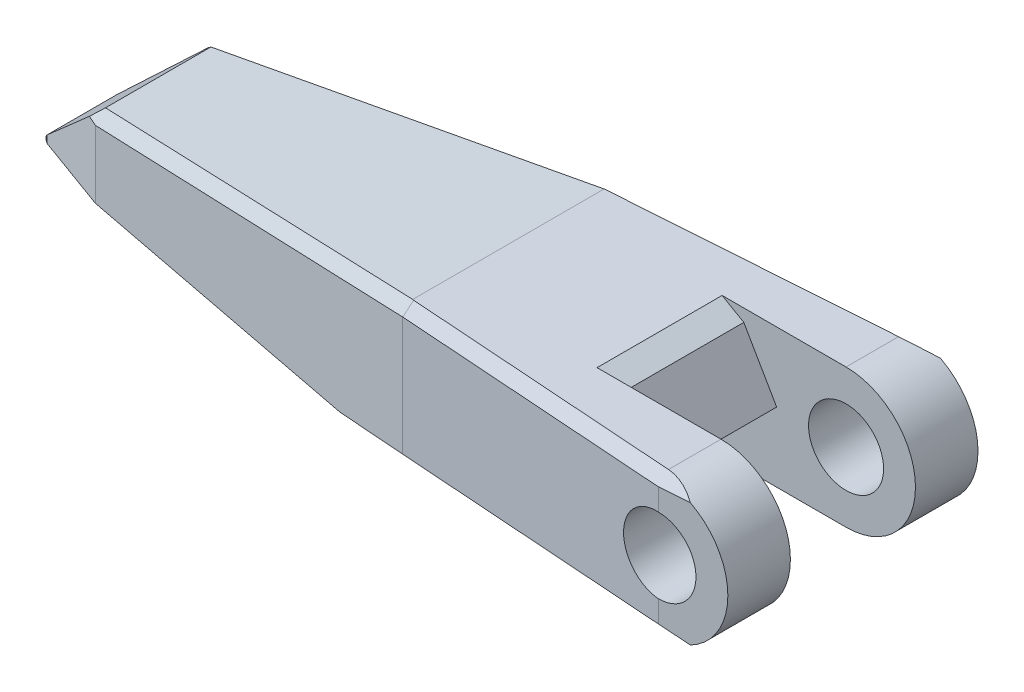
SolidWorks part; units mm, degrees
ref_plane "Alzado" through (0, 0, 0) normal (0, 0, 1) x (1, 0, 0)
ref_plane "Planta" through (0, 0, 0) normal (0, 1, 0) x (1, 0, 0)
ref_plane "Vista lateral" through (0, 0, 0) normal (1, 0, 0) x (0, 0, -1)
sketch "Croquis1" plane through (0, 0, 0) normal (0, 0, 1) x (1, 0, 0)
  line L0 (-56.8432, -15.5) -> (-41.8432, -15.5)
  line L1 (-41.8432, -15.5) -> (-41.8432, 0)
  line L3 (-41.8432, -15.5) -> (28.1568, -21.6242)
  line L4 (28.1568, -21.6242) -> (28.1568, 6.1242)
  line L5 (28.1568, 6.1242) -> (-41.8432, 0)
  line L6 (48.1568, 6.1242) -> (48.1568, -21.6242)
  line L7 (48.1568, -21.6242) -> (28.1568, -21.6242)
  line L8 (28.1568, 6.1242) -> (48.1568, 6.1242)
  line L9 (48.1568, 6.1242) -> (83.1568, 6.1242)
  line L10 (48.1568, -21.6242) -> (83.1568, -21.6242)
  line L11 (-57.0307, -14.0347) -> (-41.8432, 0)
  arc A0 (83.1568, -21.6242) -> (83.1568, 6.1242) centre (83.1568, -7.75) ccw
  circle A1 centre (83.1568, -7.75) radius 7.5
  ellipse E0 centre (-56.8686, -14.7363) end of major axis (-56.8941, -13.9726) minor radius 0.3641 (-57.0307, -14.0347) -> (-56.8432, -15.5) ccw
  point P12 (97.0311, -7.75)
  dimension "D8" = 15
  dimension "D1" = 15.5
  dimension "D2" = 15
  dimension "D3" = 90
  dimension "D4" = 85
  dimension "D5" = 85
  dimension "D6" = 70
  dimension "D7" = 20
  dimension "D9" = 27.7484
  dimension "D10" = 35
  dimension "D11" = 35
  dimension "D12" = 154.2636
extrude "Saliente-Extruir1" add sketch "Croquis1" along normal blind 50 contours L11 E0 L0 L1 | L4 L5 L1 L3 | L8 L4 L7 L6 | L10 A0 L9 L6 A1 region at (-47.3575, -10.2977, 0) region at (-3.539, -7.75, 0) region at (38.1568, -7.75, 0) region at (69.2849, -7.75, 0)
sketch "Croquis2" plane through (-0.3178, 3.633, 0) normal (-0.0872, 0.9962, 0) x (0.9962, 0.0872, 0)
  line L0 (83.3742, 0) -> (28.6289, -3.8282)
  line L1 (28.6289, -3.8282) -> (-41.6839, -12.4615)
  line L2 (28.6289, -3.8282) -> (28.5835, -46.1687)
  line L3 (28.5835, -50) -> (28.5835, 0) construction
  line L4 (-41.6839, -50) -> (-41.6839, 0) construction
  line L5 (-41.6839, -12.4615) -> (-41.6839, -37.5409)
  line L6 (28.5835, -46.1687) -> (83.3742, -50)
  line L7 (83.3742, -50) -> (83.3742, 0)
  line L8 (28.5835, 0) -> (83.3742, 0) construction
  line L9 (28.5835, -50) -> (83.3742, -50) construction
  line L10 (-41.6839, -37.5409) -> (28.5835, -46.1687)
  line L11 (28.5835, 0) -> (-41.6839, 0) construction
  line L12 (28.5835, -50) -> (-41.6839, -50) construction
  line L13 (-41.6839, -12.4615) -> (-58.0369, -18.4135)
  line L14 (-58.0369, -50) -> (-58.0369, 0) construction
  line L15 (-58.0369, -18.4135) -> (-58.0369, -31.5889)
  line L16 (-58.0369, -31.5889) -> (-41.6839, -37.5409)
  line L17 (-58.0369, -18.4135) -> (-58.3025, -18.4135)
  line L18 (-58.3025, 0) -> (-58.3025, -50) construction
  line L19 (-58.3025, -18.4135) -> (-58.3025, -31.5889)
  line L20 (-58.3025, -31.5889) -> (-58.0369, -31.5889)
  line L21 (-58.3025, -18.4135) -> (-58.3025, 0)
  line L22 (-58.3025, 0) -> (-41.6839, 0)
  line L23 (-41.6839, 0) -> (-41.6839, -12.4615)
  line L24 (-58.3025, -31.5889) -> (-58.3025, -50)
  line L25 (-58.3025, -50) -> (-41.6839, -50)
  line L26 (-41.6839, -50) -> (-41.6839, -37.5409)
  dimension "D1" = 4
  dimension "D2" = 4
  dimension "D3" = 42.3405
  dimension "D4" = 7
  dimension "D5" = 7
  dimension "D6" = 25.0794
  dimension "D7" = 70
  dimension "D8" = 70
sketch "Croquis6" plane through (0, 6.1242, 0) normal (0, 1, 0) x (1, 0, 0)
  line L0 (28.1568, 0) -> (28.1568, -3.846)
  line L1 (28.1568, -50) -> (28.1568, 0) construction
  line L2 (28.1568, -3.846) -> (83.1568, 0)
  line L3 (83.1568, 0) -> (28.1568, 0)
  line L4 (28.1568, -46.154) -> (28.1568, -50)
  line L5 (28.1568, -50) -> (83.1568, -50)
  line L6 (83.1568, -50) -> (28.1568, -46.154)
  line L7 (28.1568, -46.154) -> (-41.8432, -37.5591)
  line L8 (-41.8432, -50) -> (-41.8432, 0) construction
  line L9 (-41.8432, -37.5591) -> (-41.8432, -50)
  line L10 (-41.8432, -50) -> (28.1568, -50)
  line L11 (28.1568, -3.846) -> (-41.8432, -12.4409)
  line L12 (-41.8432, -12.4409) -> (-41.8432, 0)
  line L13 (-41.8432, 0) -> (28.1568, 0)
  line L14 (28.1568, -46.154) -> (28.1568, -50)
  line L15 (28.1568, 0) -> (28.1568, -3.846)
  line L16 (-41.8432, -12.4409) -> (-57.0307, -17.9687)
  line L17 (-57.0307, -50) -> (-57.0307, 0) construction
  line L18 (-57.0307, -17.9687) -> (-57.2334, -17.9687)
  line L19 (-57.2334, 0) -> (-57.2334, -50) construction
  line L20 (-57.2334, -17.9687) -> (-57.2334, 0)
  line L21 (-57.2334, 0) -> (-41.8432, 0)
  line L22 (-41.8432, -37.5591) -> (-57.0307, -32.0313)
  line L23 (-57.0307, -32.0313) -> (-57.2334, -32.0313)
  line L24 (-57.2334, -32.0313) -> (-57.2334, -50)
  line L25 (-57.2334, -50) -> (-41.8432, -50)
  line M11 (83.1568, 0) -> (28.1568, 0)
  line M12 (28.1568, 0) -> (28.1568, -50)
  line M13 (28.1568, -50) -> (83.1568, -50)
  dimension "D1" = 4
  dimension "D2" = 4
  dimension "D3" = 7
  dimension "D4" = 7
  dimension "D5" = 70
  dimension "D6" = 70
extrude "Cortar-Extruir4" cut sketch "Croquis6" against normal blind 50 contours L2 M12 M11 | L6 M13 M12 | L9 L10 L7 M12 | L13 L12 L11 M12 | L21 L20 L18 L16 L12 | L24 L25 L9 L22 L23 region at (46.4902, 6.1242, 1.282) region at (46.4902, 6.1242, 48.718) region at (-12.9999, 6.1242, 45.5503) region at (-12.9999, 6.1242, 4.4497) region at (-50.0094, 6.1242, 7.7063) region at (-50.0094, 6.1242, 42.2937)
sketch "Croquis8" plane through (0, 6.1242, 0) normal (0, 1, 0) x (1, 0, 0)
  line L0 (83.1568, -15) -> (67.4431, -15)
  line L1 (83.1568, -50) -> (83.1568, 0) construction
  line L2 (67.4431, -15) -> (67.4431, -35)
  line L3 (67.4431, -35) -> (83.1568, -35)
  line L4 (83.1568, -35) -> (97.0311, -35)
  line L5 (97.0311, -50) -> (97.0311, 0) construction
  line L6 (97.0311, -35) -> (97.0311, -15)
  line L7 (97.0311, -15) -> (83.1568, -15)
  line L8 (97.0311, 0) -> (83.1568, 0) construction
  line L9 (67.4431, -15) -> (97.0311, -15)
  line L10 (67.4431, -15) -> (67.4431, -35)
  line L11 (67.4431, -35) -> (97.0311, -35)
  line L12 (97.0311, -15) -> (97.0311, -35)
  line L13 (83.1568, -50) -> (97.0311, -50) construction
  dimension "D1" = 50
  dimension "D2" = 15
  dimension "D3" = 20
  dimension "D4" = 15
sketch "Croquis9" plane through (0, 0, 0) normal (1, 0, 0) x (0, 0, -1)
  line L0 (-25, 6.1242) -> (-25, -21.619)
  line L1 (-15, 6.1242) -> (-35, 6.1242) construction
ref_plane "Plano2" through (0, 0, 25) normal (0, 0, 1) x (1, 0, 0)
sketch "Croquis10" plane through (0, 0, 25) normal (0, 0, 1) x (1, 0, 0)
  line L0 (83.1568, 6.1242) -> (75.7316, 6.1242)
  line L1 (83.1568, 6.1242) -> (28.1568, 6.1242) construction
  line L2 (75.7316, 6.1242) -> (75.7316, 3.97)
  line L3 (83.1568, -21.6242) -> (76.457, -21.6242)
  line L4 (28.1568, -21.6242) -> (83.1568, -21.6242) construction
  line L5 (76.457, -21.6242) -> (76.457, -19.8993)
  arc A0 (83.1568, -21.6242) -> (83.1568, 6.1242) centre (83.1568, -7.75) ccw
  arc A1 (75.7316, 3.97) -> (76.457, -19.8993) centre (83.1568, -7.75) ccw
extrude "Cortar-Extruir6" cut sketch "Croquis10" against normal mid plane 25
sketch "Croquis14" plane through (-3.0747, 0, 43.9701) normal (-0.0698, 0, 0.9976) x (0.9976, 0, 0.0698)
  line L0 (31.3078, 6.1242) -> (31.3078, 4.1242) construction
  line L1 (31.3078, -21.6242) -> (31.3078, 6.1242) construction
  line L2 (31.3078, 4.1242) -> (86.4421, 4.1242) construction
  line L3 (86.4421, -0.25) -> (86.4421, 6.1242) construction
  line L4 (86.4421, 6.1242) -> (31.3078, 6.1242) construction
  dimension "D1" = 2
sketch "Croquis15" plane through (0, 6.1242, 0) normal (0, 1, 0) x (1, 0, 0)
  line L0 (28.1568, -46.154) -> (28.1568, -44.154) construction
  line L1 (28.1568, -46.154) -> (28.1568, -3.846) construction
  line L2 (28.1568, -44.154) -> (83.1568, -48) construction
  line L3 (83.1568, -50) -> (83.1568, -37.5) construction
  line L4 (83.1568, -48) -> (83.1568, -50) construction
  dimension "D1" = 2
  dimension "D2" = 2
ref_plane "Plano5" through (-1.6849, 24.0957, 24.0957) normal (-0.0494, 0.7062, 0.7062) x (0.9988, 0.0349, 0.0349)
sketch "Croquis16" plane through (-1.6849, 24.0957, 24.0957) normal (-0.0494, 0.7062, 0.7062) x (0.9988, 0.0349, 0.0349)
  line L0 (29.8782, -26.8911) -> (29.9481, -28.3054)
  line L1 (29.9481, -28.3054) -> (29.8782, -29.7196)
  line L2 (29.8782, -29.7196) -> (84.9454, -32.4391)
  line L3 (84.9454, -32.4391) -> (85.0153, -31.0249)
  line L4 (85.0153, -31.0249) -> (84.9454, -29.6107)
  line L5 (84.9454, -29.6107) -> (29.8782, -26.8911)
chamfer "Chaflán3" distance 2 angle 45 1 edges at (55.6568, 6.1242, 1.923)
chamfer "Chaflán4" distance 2 angle 45 1 edges at (-13.9749, 2.4382, 9.0191) first distance on face at (-2.6959, 3.4249, 21.5204)
chamfer "Chaflán5" distance 2 angle 45 1 edges at (-6.8432, 3.0621, 41.8566) first distance on face at (-6.8432, -7.75, 41.8566)
chamfer "Chaflán6" distance 2 angle 45 1 edges at (55.6568, -21.6242, 48.077)
chamfer "Chaflán9" distance 2 angle 45 1 edges at (55.6568, -21.6242, 1.923)
chamfer "Chaflán10" distance 2 angle 45 1 edges at (62.8476, 6.1242, 48.5798)
sketch "Croquis17" plane through (0, 0, 0) normal (0, 1, 0) x (1, 0, 0)
  line L0 (83.1568, -12.5) -> (75.7316, -12.5) construction
  line L1 (79.4442, -12.5) -> (73.4442, -12.5)
  line L2 (79.4442, -12.5) -> (79.4442, -37.5)
  line L3 (79.4442, -37.5) -> (73.4442, -37.5)
  line L4 (73.4442, -12.5) -> (73.4442, -37.5)
  line L5 (83.1568, -37.5) -> (75.7316, -37.5) construction
  dimension "D1" = 6
extrude "Cortar-Extruir8" cut sketch "Croquis17" against normal mid plane 100
sketch "Croquis18" plane through (0, 0, 0) normal (0, 1, 0) x (1, 0, 0)
  line L2 (97.9233, -25) -> (51.5424, -25) construction
ref_plane "Plano6" through (0, 0, 25) normal (0, 0, 1) x (1, 0, 0)
sketch "Croquis19" plane through (0, 0, 25) normal (0, 0, 1) x (1, 0, 0)
  line L0 (97.0311, -7.75) -> (83.1568, -7.75) construction
  line L1 (63.3424, 6.1242) -> (83.1568, 6.1242)
  line L2 (83.1568, -7.75) -> (63.3424, 6.1242)
  line L3 (28.3812, 6.1242) -> (83.1568, 6.1242) construction
  line L4 (83.1568, 6.1242) -> (83.1568, -7.75)
  line L5 (83.1568, -7.75) -> (83.1568, -21.6242)
  line L6 (83.1568, -21.6242) -> (63.3424, -21.6242)
  line L7 (83.1568, -21.6242) -> (28.1568, -21.6242) construction
  line L8 (63.3424, -21.6242) -> (83.1568, -7.75)
  arc A0 (89.5386, -20.0694) -> (89.5386, 4.5694) centre (83.1568, -7.75) ccw construction
  dimension "D1" = 55
  dimension "D2" = 55
extrude "Cortar-Extruir9" cut sketch "Croquis19" against normal mid plane 25 contours L4 L1 L2 | L8 L6 L5 region at (76.552, -16.9995, 25) region at (76.552, 1.4995, 25)
sketch "Croquis20" plane through (0, 0, 25) normal (0, 0, 1) x (1, 0, 0)
  line L0 (69.2826, -7.75) -> (61.2724, 6.1242)
  line L1 (28.3812, 6.1242) -> (83.1568, 6.1242) construction
  line L2 (61.2724, 6.1242) -> (83.1568, 6.1242)
  line L5 (61.2724, 6.1242) -> (57.2223, 13.139)
  line L7 (83.1568, -21.6242) -> (28.1568, -21.6242) construction
  line L8 (69.2826, -7.75) -> (61.2724, -21.6242)
  line L9 (61.2724, -21.6242) -> (83.1568, -21.6242)
  arc A0 (83.1568, 6.1242) -> (83.1568, -21.6242) centre (83.1568, -7.75) ccw
  dimension "D1" = 180
  dimension "D2" = 60
extrude "Cortar-Extruir10" cut sketch "Croquis20" against normal mid plane 25 contours A0 L2 L0 | A0 L8 L9 region at (69.0726, -17.65, 25) region at (69.0726, 2.15, 25)
sketch "Croquis22" plane through (48.6061, 28.0628, 0) normal (0.866, 0.5, 0) x (0, 0, -1)
  line L0 (-12.5, -36.2747) -> (-12.5, -62.1643) construction
  line L1 (-37.5, -41.353) -> (-12.5, -41.353)
  line L2 (-37.5, -41.353) -> (-37.5, -52.6763)
  line L3 (-37.5, -52.6763) -> (-12.5, -52.6763)
  line L4 (-12.5, -41.353) -> (-12.5, -52.6763)
extrude "Cortar-Extruir11" cut sketch "Croquis22" against normal through all
ref_plane "Plano7" through (100, 0, 0) normal (1, 0, 0) x (0, 0, -1)
sketch "Croquis23" plane through (100, 0, 0) normal (1, 0, 0) x (0, 0, -1)
  line L0 (-37.5, -21.6242) -> (-37.5, 6.1242) construction
  line L1 (-37.5, -12.75) -> (-12.5, -12.75)
  line L2 (-37.5, -12.75) -> (-37.5, -29.0937)
  line L3 (-37.5, -29.0937) -> (-12.5, -29.0937)
  line L4 (-12.5, -12.75) -> (-12.5, -29.0937)
  line L5 (-12.5, 6.1242) -> (-12.5, -21.6242) construction
  line L6 (-12.5, -7.75) -> (-37.5, -7.75) construction
  point P8 (-37.5, -29.0937)
  dimension "D1" = 5
extrude "Cortar-Extruir12" cut sketch "Croquis23" against normal blind 80
fillet "Chaflán14" radius 5 1 edges at (60.6224, -12.75, 25) profile chamfer
fillet "Chaflán15" radius 5 1 edges at (61.2724, 6.1242, 25) profile chamfer
chamfer "Chaflán17" distance 9 angle 45 1 edges at (20, -20.9106, 25) first distance on face at (9.6728, -20.0071, 25)
